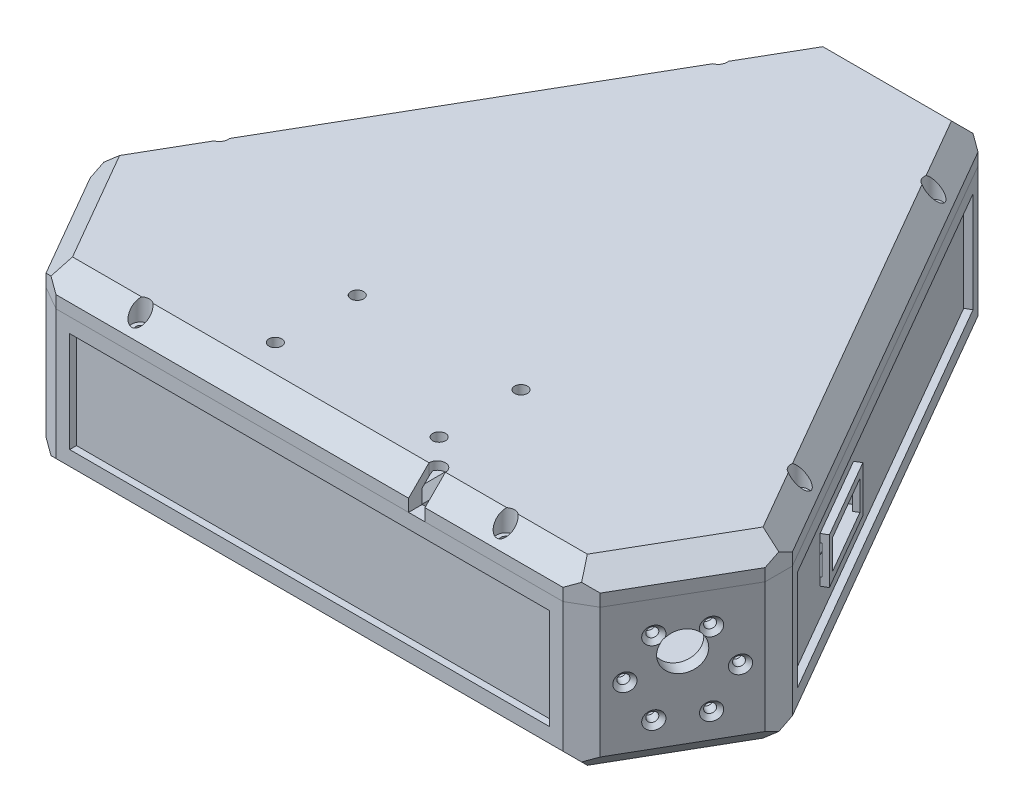
SolidWorks part; units mm, degrees
note: '?' marks a value the reader was unsure of.
ref_plane "Front Plane" through (0, 0, 0) normal (0, 0, 1) x (1, 0, 0)
ref_plane "Top Plane" through (0, 0, 0) normal (0, 1, 0) x (1, 0, 0)
ref_plane "Right Plane" through (0, 0, 0) normal (1, 0, 0) x (0, 0, -1)
ref_axis "Axis1" through (0, 27.75, 0) along (0, -1, 0)?
sketch "Sketch1" plane through (0, 0, 0) normal (0, 1, 0) x (1, 0, 0)
  line L0 (-120.7532, -40.8494) -> (-95.7532, -84.1506)
  line L1 (-95.7532, -84.1506) -> (95.7532, -84.1506)
  line L2 (95.7532, -84.1506) -> (120.7532, -40.8494)
  line L3 (120.7532, -40.8494) -> (25, 125)
  line L4 (25, 125) -> (-25, 125)
  line L5 (-25, 125) -> (-120.7532, -40.8494)
  line L6 (-117.2532, -46.9115) -> (-99.2532, -78.0885) construction
  line L7 (0, 125) -> (0, 0) construction
  line L8 (0, 0) -> (-108.2532, -62.5) construction
  line L9 (0, 0) -> (108.2532, -62.5) construction
  arc A0 (-12.9904, -7.5) -> (12.9904, -7.5) centre (0, 0) ccw construction
  arc A1 (12.9904, -7.5) -> (0, 15) centre (0, 0) ccw construction
  arc A2 (0, 15) -> (-12.9904, -7.5) centre (0, 0) ccw construction
  dimension "D1" = 50
  dimension "D2" = 15
extrude "Outer Ring" add sketch "Sketch1" along normal mid plane 50 thin
sketch "Sketch2" plane through (0, -25, 0) normal (0, -1, 0) x (1, 0, 0)
  line L6 (-126.5267, 40.8494) -> (-27.8868, -130)
  line L7 (-27.8868, -130) -> (27.8868, -130)
  line L8 (27.8868, -130) -> (126.5267, 40.8494)
  line L9 (126.5267, 40.8494) -> (98.6399, 89.1506)
  line L10 (98.6399, 89.1506) -> (-98.6399, 89.1506)
  line L11 (-98.6399, 89.1506) -> (-126.5267, 40.8494)
  line L12 (-126.5267, 40.8494) -> (-27.8868, -130)
  line L13 (-27.8868, -130) -> (27.8868, -130)
  line L14 (27.8868, -130) -> (126.5267, 40.8494)
  line L15 (126.5267, 40.8494) -> (98.6399, 89.1506)
  line L16 (98.6399, 89.1506) -> (-98.6399, 89.1506)
  line L17 (-98.6399, 89.1506) -> (-126.5267, 40.8494)
  dimension "D1" = 0
extrude "Bottom Plate" add sketch "Sketch2" along normal blind 5
fillet "Corner Reinforcement" radius 15 6 edges at (-25, 0, -125) (25, 0, -125) (120.7532, 0, 40.8494) (95.7532, 0, 84.1506) (-95.7532, 0, 84.1506) (-120.7532, 0, 40.8494)
sketch "Sketch3" plane through (0, 25, 0) normal (0, 1, 0) x (1, 0, 0)
  line L0 (-22.1132, 130) -> (-30.7735, 125)
  line L1 (27.8868, 130) -> (-27.8868, 130) construction
  line L2 (-27.8868, 130) -> (-126.5267, -40.8494) construction
  line L3 (22.1132, 130) -> (30.7735, 125)
  line L4 (126.5267, -40.8494) -> (27.8868, 130) construction
  line L5 (-30.7735, 125) -> (-27.8868, 130)
  line L6 (-27.8868, 130) -> (-22.1132, 130)
  line L7 (22.1132, 130) -> (27.8868, 130)
  line L8 (27.8868, 130) -> (30.7735, 125)
  dimension "D1" = 10
extrude "Corner Chamfers" cut sketch "Sketch3" against normal through all both and the other way through all
sketch "Sketch4" plane through (0, 0, -130) normal (0, 0, -1) x (-1, 0, 0)
  circle A0 centre (0, 7) radius 7
  circle A1 centre (0, 7) radius 6 construction
  circle A2 centre (-7.75, 13.4234) radius 1.75
  circle A3 centre (7.75, 13.4234) radius 1.75
  circle A4 centre (-15.5, 0) radius 1.75
  circle A5 centre (15.5, 0) radius 1.75
  circle A6 centre (-7.75, -13.4234) radius 1.75
  circle A7 centre (7.75, -13.4234) radius 1.75
  dimension "D1" = 1
  dimension "D2" = 3.5
extrude "Motor Holes" cut sketch "Sketch4" against normal blind 15
chamfer "Motor Countersinks" distance 1.5 angle 45 6 edges at (-17.25, 0, -130) (-9.5, -13.4234, -130) (6, -13.4234, -130) (13.75, 0, -130) (-9.5, 13.4234, -130) (6, 13.4234, -130)
pattern_circular "CirPattern1" count 3 over 360 about axis through (0, 0, 0) along (0, 1, 0) of "Motor Holes", "Motor Countersinks", "Corner Chamfers"
chamfer "Base Chamfers" distance 7.5 angle 45 18 edges at (0, -30, -130) (-77.2067, -30, -44.5753) (-112.5833, -30, 65) (0, -30, 89.1506) (112.5833, -30, 65) (77.2067, -30, -44.5753) (108.2532, -25, 62.5) (118.4327, -25, 40.8494) (94.5929, -25, 82.141) (72.8766, -25, -42.0753) (0, -25, 84.1506) (23.8397, -25, -122.9904) (-94.5929, -25, 82.141) (0, -25, -125) (-108.2532, -25, 62.5) (-23.8397, -25, -122.9904) (-118.4327, -25, 40.8494) (-72.8766, -25, -42.0753)
sketch "Sketch5" plane through (0, 0, -125) normal (0, 0, 1) x (1, 0, 0)
  circle A0 centre (0, 0) radius 21.25
  circle A1 centre (0, 0) radius 17.25 construction
  circle A2 centre (7.75, 13.4234) radius 1.75 construction
  circle A3 centre (-15.5, 0) radius 1.75 construction
  circle A4 centre (7.75, -13.4234) radius 1.75 construction
  dimension "D1" = 42.5
extrude "Motor Front Clearance" cut sketch "Sketch5" along normal blind 10
sketch "Sketch12" plane through (0, 25, 0) normal (0, 1, 0) x (1, 0, 0)
  line L1 (-29.3301, 117.5) -> (-116.423, -33.3494) construction
  line L5 (29.3301, 117.5) -> (116.423, -33.3494) construction
  line L8 (-36.9338, 104.3301) -> (-41.9338, 95.6699)
  line L9 (36.9338, 104.3301) -> (41.9338, 95.6699)
  line L11 (116.423, -33.3494) -> (29.3301, 117.5) construction
  line L12 (-116.423, -33.3494) -> (-29.3301, 117.5) construction
  line L13 (-39.4338, 100) -> (39.4338, 100) construction
  line L14 (-12.0546, 125) -> (12.0546, 125) construction
  arc A3 (-41.9338, 95.6699) -> (-36.9338, 104.3301) centre (-39.4338, 100) ccw
  arc A5 (36.9338, 104.3301) -> (41.9338, 95.6699) centre (39.4338, 100) ccw
  dimension "D1" = 5
  dimension "D3" = 25
extrude "Lid Lug Bosses" add sketch "Sketch12" against normal blind 7.5
sketch "Sketch13" plane through (0, 25, 0) normal (0, 1, 0) x (1, 0, 0)
  circle A0 centre (-39.4338, 100) radius 2.35
  circle A1 centre (39.4338, 100) radius 2.35
  arc A2 (36.9338, 104.3301) -> (41.9338, 95.6699) centre (39.4338, 100) ccw construction
  arc A3 (-41.9338, 95.6699) -> (-36.9338, 104.3301) centre (-39.4338, 100) ccw construction
  dimension "D1" = 4.7
extrude "Lid Lug Heatset Insert Holes" cut sketch "Sketch13" against normal blind 4
pattern_circular "Lid Lug Pattern" count 3 over 360 about axis through (0, 0, 0) along (0, 1, 0) of "Motor Front Clearance", "Lid Lug Bosses", "Lid Lug Heatset Insert Holes"
chamfer "Lid Lug Chamfer" distance 7.5 angle 30 6 edges at (39.4338, 17.5, -100) (-39.4338, 17.5, -100) (106.3194, 17.5, 15.8494) (66.8857, 17.5, 84.1506) (-66.8857, 17.5, 84.1506) (-106.3194, 17.5, 15.8494)
sketch "Sketch14" plane through (0, 25, 0) normal (0, 1, 0) x (1, 0, 0)
  circle A0 centre (-39.4338, 100) radius 1.75
  circle A1 centre (39.4338, 100) radius 1.75
  circle A2 centre (-106.3194, -15.8494) radius 1.75
  circle A3 centre (-66.8857, -84.1506) radius 1.75
  circle A4 centre (66.8857, -84.1506) radius 1.75
  circle A5 centre (106.3194, -15.8494) radius 1.75
  dimension "D1" = 3.5
extrude "Lid Lug Bolt Clearance" cut sketch "Sketch14" against normal blind 8
fillet "Lid Lug Fillet" radius 3 12 edges at (41.9338, 19.0849, -95.6699) (36.9338, 19.0849, -104.3301) (-36.9338, 19.0849, -104.3301) (-41.9338, 19.0849, -95.6699) (103.8194, 19.0849, 11.5192) (108.8194, 19.0849, 20.1795) (71.8857, 19.0849, 84.1506) (61.8857, 19.0849, 84.1506) (-71.8857, 19.0849, 84.1506) (-61.8857, 19.0849, 84.1506) (-108.8194, 19.0849, 20.1795) (-103.8194, 19.0849, 11.5192)
sketch "Sketch6" plane through (0, -25, 0) normal (0, 1, 0) x (1, 0, 0)
  line L0 (-55.5, 38.5) -> (-55.5, 16.5) construction
  line L1 (-44, 50) -> (44, 50) construction
  line L2 (55.5, 38.5) -> (55.5, 16.5) construction
  line L4 (44, 5) -> (-44, 5) construction
  line L9 (-56.5, 16.5) -> (-56.5, 38.5)
  line L10 (-55.5, 27.5) -> (55.5, 27.5) construction
  line L11 (56.5, 16.5) -> (56.5, 38.5)
  line L23 (-44, 51) -> (44, 51)
  line L24 (-44, 54) -> (44, 54)
  line L25 (-44, 4) -> (44, 4)
  line L26 (-44, 1) -> (44, 1)
  line L27 (-59.5, 38.5) -> (-59.5, 16.5)
  line L28 (59.5, 38.5) -> (59.5, 16.5)
  arc A0 (-44, 51) -> (-56.5, 38.5) centre (-44, 38.5) ccw
  arc A1 (44, 4) -> (56.5, 16.5) centre (44, 16.5) ccw
  arc A2 (-54.776, 20.5159) -> (-39.9841, 5.724) centre (-44, 16.5) ccw construction
  arc A3 (-39.9841, 49.276) -> (-54.776, 34.4841) centre (-44, 38.5) ccw construction
  arc A4 (54.776, 34.4841) -> (39.9841, 49.276) centre (44, 38.5) ccw construction
  arc A5 (39.9841, 5.724) -> (54.776, 20.5159) centre (44, 16.5) ccw construction
  arc A6 (-44, 54) -> (-59.5, 38.5) centre (-44, 38.5) ccw
  arc A7 (44, 1) -> (59.5, 16.5) centre (44, 16.5) ccw
  arc A8 (44, 54) -> (59.5, 38.5) centre (44, 38.5) cw
  arc A9 (44, 51) -> (56.5, 38.5) centre (44, 38.5) cw
  arc A10 (-44, 1) -> (-59.5, 16.5) centre (-44, 16.5) cw
  arc A11 (-44, 4) -> (-56.5, 16.5) centre (-44, 16.5) cw
  dimension "D1" = 1
  dimension "D2" = 3
extrude "Battery Holder" add sketch "Sketch6" along normal blind 20
sketch "Sketch7" plane through (0, 0, -1) normal (0, 0, 1) x (1, 0, 0)
  line L0 (-34, -5) -> (-14, -25)
  line L1 (-44, -5) -> (44, -5) construction
  line L2 (-44, -25) -> (44, -25) construction
  line L3 (-14, -25) -> (14, -25)
  line L4 (14, -25) -> (34, -5)
  line L5 (34, -5) -> (-34, -5)
  line L6 (-44, -5) -> (-44, -25) construction
  point P7 (0, -25)
  point P9 (0, -5)
  dimension "D1" = 45
  dimension "D2" = 10
extrude "Battery Holder Chamfer" cut sketch "Sketch7" against normal up to surface (53 mm away) up to face at (0, -15, -54)
sketch "Sketch8" plane through (0, -25, 0) normal (0, 1, 0) x (1, 0, 0)
  line L0 (0, 0) -> (17, -24.24) construction
  line L1 (-2.05, -9) -> (36.05, -9) construction
  line L2 (-2.05, -9) -> (-2.05, -39.48) construction
  line L3 (-2.05, -39.48) -> (36.05, -39.48) construction
  line L4 (36.05, -9) -> (36.05, -39.48) construction
  line L9 (-2.05, -9) -> (36.05, -39.48) construction
  line L11 (-44, 1) -> (-14, 1) construction
  circle A0 centre (-2.05, -9) radius 2.35
  circle A1 centre (36.05, -9) radius 2.35
  circle A2 centre (-2.05, -39.48) radius 2.35
  circle A3 centre (36.05, -39.48) radius 2.35
  circle A8 centre (36.05, -9) radius 5
  circle A9 centre (-2.05, -9) radius 5
  circle A10 centre (-2.05, -39.48) radius 5
  circle A11 centre (36.05, -39.48) radius 5
  point P7 (17, -24.24)
  dimension "D1" = 38.1
  dimension "D3" = 4.7
  dimension "D4" = 10
  dimension "D2" = 30.48
  dimension "D5" = 10
  dimension "D6" = 17
extrude "Motor Controller Mount" add sketch "Sketch8" along normal blind 15
sketch "Sketch9" plane through (0, -25, 0) normal (0, 1, 0) x (1, 0, 0)
  line L0 (-34, 1) -> (-14, 1) construction
  line L1 (-35.5, -4) -> (-12.45, -4) construction
  line L2 (-35.5, -4) -> (-35.5, -62.05) construction
  line L3 (-35.5, -62.05) -> (-12.45, -62.05) construction
  line L4 (-12.45, -4) -> (-12.45, -62.05) construction
  circle A0 centre (-35.5, -4) radius 0.85
  circle A1 centre (-12.45, -4) radius 0.85
  circle A2 centre (-35.5, -62.05) radius 0.85
  circle A3 centre (-12.45, -62.05) radius 0.85
  circle A4 centre (-35.5, -4) radius 3
  circle A5 centre (-12.45, -4) radius 3
  circle A6 centre (-12.45, -62.05) radius 3
  circle A7 centre (-35.5, -62.05) radius 3
  dimension "D1" = 58.05
  dimension "D3" = 1.7
  dimension "D4" = 6
  dimension "D5" = 5
  dimension "D2" = 23.05
  dimension "D6" = 35.5
extrude "Pi Zero Mount" add sketch "Sketch9" along normal blind 5
chamfer "Chamfer2" distance 3 angle 30 4 edges at (-35.5, -25, 59.05) (-12.45, -25, 59.05) (-35.5, -25, 1) (-12.45, -25, 1)
chamfer "Chamfer3" distance 7.5 angle 30 4 edges at (-2.05, -25, 4) (36.05, -25, 4) (36.05, -25, 34.48) (-2.05, -25, 34.48)
sketch "Sketch10" plane through (0, 0, 84.1506) normal (0, 0, -1) x (-1, 0, 0)
  line L0 (51.975, 19.85) -> (51.975, 16.85)
  line L1 (51.975, 16.85) -> (61.975, 16.85)
  line L2 (61.975, 16.85) -> (61.975, -0.5)
  line L3 (61.975, -0.5) -> (51.975, -0.5)
  line L4 (51.975, -0.5) -> (51.975, -3.5)
  line L5 (51.975, -3.5) -> (61.975, -3.5)
  line L6 (61.975, -3.5) -> (64.975, -0.5)
  line L7 (64.975, -0.5) -> (64.975, 16.85)
  line L8 (64.975, 16.85) -> (61.975, 19.85)
  line L9 (61.975, 19.85) -> (51.975, 19.85)
  line L10 (-24.525, 0) -> (61.475, 0) construction
  line L11 (-24.525, 16.35) -> (61.475, 16.35) construction
  line L12 (61.475, 13.85) -> (61.475, 2.5) construction
  line L13 (61.975, 19.85) -> (61.975, 16.85) construction
  line L14 (64.975, 16.85) -> (61.975, 16.85) construction
  line L15 (18.475, 16.35) -> (18.475, 0) construction
  line L16 (-28.025, 16.85) -> (-25.025, 19.85)
  line L17 (-28.025, -0.5) -> (-28.025, 16.85)
  line L18 (-25.025, -3.5) -> (-28.025, -0.5)
  line L19 (-15.025, -3.5) -> (-25.025, -3.5)
  line L20 (-15.025, -0.5) -> (-15.025, -3.5)
  line L21 (-25.025, -0.5) -> (-15.025, -0.5)
  line L22 (-25.025, 16.85) -> (-25.025, -0.5)
  line L23 (-15.025, 16.85) -> (-25.025, 16.85)
  line L24 (-15.025, 19.85) -> (-15.025, 16.85)
  line L25 (-25.025, 19.85) -> (-15.025, 19.85)
  dimension "D1" = 0.5
  dimension "D2" = 0.5
  dimension "D3" = 0.5
  dimension "D4" = 3
  dimension "D5" = 10
extrude "USB Hub Mount" add sketch "Sketch10" along normal blind 22.5
sketch "Sketch11" plane through (28.025, 0, 0) normal (1, 0, 0) x (0, 0, -1)
  line L0 (-72.6506, 8.175) -> (-61.6506, 8.175) construction
  line L1 (-72.6506, 14.675) -> (-61.6506, 14.675)
  line L2 (-72.6506, 1.675) -> (-61.6506, 1.675)
  line L3 (-61.6506, 16.85) -> (-61.6506, -0.5) construction
  arc A0 (-72.6506, 14.675) -> (-72.6506, 1.675) centre (-72.6506, 8.175) ccw
  arc A1 (-61.6506, 1.675) -> (-61.6506, 14.675) centre (-61.6506, 8.175) ccw
  point P2 (-67.1506, 8.175)
  point P9 (-61.6506, 8.175)
  dimension "D1" = 6.5
  dimension "D2" = 11
extrude "USB Hub Cable Clearance" cut sketch "Sketch11" against normal up to next
chamfer "Chamfer4" distance 15 angle 45 4 edges at (-51.975, -2, 84.1506) (-51.975, 18.35, 84.1506) (15.025, -2, 84.1506) (15.025, 18.35, 84.1506)
chamfer "Chamfer5" distance 0.6 angle 30 24 edges at (-63.475, 18.35, 61.6506) (-64.975, 8.175, 61.6506) (-63.475, -2, 61.6506) (-56.975, -3.5, 61.6506) (-51.975, -2, 61.6506) (-56.975, -0.5, 61.6506) (-61.975, 8.175, 61.6506) (-56.975, 16.85, 61.6506) (-51.975, 18.35, 61.6506) (-56.975, 19.85, 61.6506) (20.025, -0.5, 61.6506) (15.025, -2, 61.6506) (20.025, -3.5, 61.6506) (26.525, -2, 61.6506) (28.025, 0.5875, 61.6506) (26.525, 1.675, 61.6506) (25.025, 0.5875, 61.6506) (26.525, 18.35, 61.6506) (20.025, 19.85, 61.6506) (15.025, 18.35, 61.6506) (20.025, 16.85, 61.6506) (25.025, 15.7625, 61.6506) (26.525, 14.675, 61.6506) (28.025, 15.7625, 61.6506)
sketch "Sketch15" plane through (0, 0, 84.1506) normal (0, 0, -1) x (-1, 0, 0)
  line L1 (61.975, 16.85) -> (59.4695, 16.85)
  line L2 (61.975, 16.85) -> (61.975, 13.1699)
  line L3 (61.975, 13.1699) -> (59.4695, 13.1699)
  line L4 (59.4695, 16.85) -> (59.4695, 13.1699)
extrude "USB Hub Area Lid Lug Removal" cut sketch "Sketch15" along normal up to surface (22.5 mm away) up to face at (-58.6849, 8.175, 61.6506)
sketch "Sketch20" plane through (0, -25, 0) normal (0, 1, 0) x (1, 0, 0)
  line L0 (-98.4384, -17.199) -> (-80.2518, -27.699) construction
  line L1 (-98.4384, -17.199) -> (-76.4384, 20.9061) construction
  line L2 (-80.2518, -27.699) -> (-58.2518, 10.4061) construction
  line L3 (-76.4384, 20.9061) -> (-58.2518, 10.4061) construction
  line L4 (-22.8349, 113.75) -> (-109.9279, -37.0994) construction
  line L5 (-94.6884, -10.7038) -> (-92.7041, -11.8494) construction
  line L6 (-92.7041, -11.8494) -> (-96.4541, -18.3446) construction
  line L7 (-60.2361, 11.5518) -> (-63.9861, 5.0566) construction
  line L8 (-63.9861, 5.0566) -> (-62.0018, 3.9109) construction
  arc A0 (-59.5, 16.5) -> (-44, 1) centre (-44, 16.5) ccw construction
  circle A1 centre (-63.9861, 5.0566) radius 0.85
  circle A2 centre (-92.7041, -11.8494) radius 0.85
  circle A3 centre (-92.7041, -11.8494) radius 3.375
  circle A4 centre (-63.9861, 5.0566) radius 3.375
  dimension "D3" = 7.5
  dimension "D5" = 1.7
  dimension "D6" = 6.75
  dimension "D1" = 44
  dimension "D2" = 21
  dimension "D4" = 2.2913
extrude "Buck Converter Mount" add sketch "Sketch20" along normal blind 5
sketch "Sketch21" plane through (77.2067, 0, -44.5753) normal (0.866, 0, -0.5) x (-0.5, 0, -0.866)
  line L1 (-52.8664, 6.625) -> (-25.3664, 6.625)
  line L2 (-52.8664, 6.625) -> (-52.8664, -4.125)
  line L3 (-52.8664, -4.125) -> (-25.3664, -4.125)
  line L4 (-25.3664, 6.625) -> (-25.3664, -4.125)
  line L5 (-92.8664, -22.5) -> (-92.8664, 25) construction
  line L6 (-52.8664, 25) -> (-52.8664, 6.625) construction
  line L7 (-92.8664, 25) -> (92.8664, 25) construction
  line L8 (-52.8664, -4.125) -> (-52.8664, -22.5) construction
  line L9 (-92.8664, -22.5) -> (92.8664, -22.5) construction
  dimension "D1" = 27.5
  dimension "D2" = 10.75
  dimension "D4" = 40
extrude "Power Switch Hole" cut sketch "Sketch21" against normal up to next
sketch "Sketch22" plane through (72.8766, 0, -42.0753) normal (-0.866, 0, 0.5) x (0.5, 0, 0.866)
  line L0 (25.3664, 6.625) -> (52.8664, 6.625) construction
  line L1 (55.8664, 6.625) -> (22.3664, 6.625)
  line L2 (55.8664, 6.625) -> (55.8664, -4.125)
  line L3 (55.8664, -4.125) -> (22.3664, -4.125)
  line L4 (22.3664, 6.625) -> (22.3664, -4.125)
  line L6 (52.8664, -4.125) -> (25.3664, -4.125) construction
  line L7 (25.3664, -4.125) -> (25.3664, 6.625) construction
  line L8 (25.3664, 6.625) -> (52.8664, 6.625) construction
  point P10 (39.1164, 6.625)
  dimension "D1" = 3
extrude "Power Switch Countersink" cut sketch "Sketch22" against normal offset from surface 2 and the other way blind 5 up to face at (96.7649, 1.25, -10.6995)
sketch "Sketch16" plane through (0, 25, 0) normal (0, 1, 0) x (1, 0, 0)
  line L12 (92.8664, -89.1506) -> (101.5267, -84.1506)
  line L13 (101.5267, -84.1506) -> (123.6399, -45.8494)
  line L14 (123.6399, -45.8494) -> (123.6399, -35.8494)
  line L15 (123.6399, -35.8494) -> (30.7735, 125)
  line L16 (30.7735, 125) -> (22.1132, 130)
  line L17 (22.1132, 130) -> (-22.1132, 130)
  line L18 (-22.1132, 130) -> (-30.7735, 125)
  line L19 (-30.7735, 125) -> (-123.6399, -35.8494)
  line L20 (-123.6399, -35.8494) -> (-123.6399, -45.8494)
  line L21 (-123.6399, -45.8494) -> (-101.5267, -84.1506)
  line L22 (-101.5267, -84.1506) -> (-92.8664, -89.1506)
  line L23 (-92.8664, -89.1506) -> (92.8664, -89.1506)
  line L24 (92.8664, -89.1506) -> (101.5267, -84.1506)
  line L25 (101.5267, -84.1506) -> (123.6399, -45.8494)
  line L26 (123.6399, -45.8494) -> (123.6399, -35.8494)
  line L27 (123.6399, -35.8494) -> (30.7735, 125)
  line L28 (30.7735, 125) -> (22.1132, 130)
  line L29 (22.1132, 130) -> (-22.1132, 130)
  line L30 (-22.1132, 130) -> (-30.7735, 125)
  line L31 (-30.7735, 125) -> (-123.6399, -35.8494)
  line L32 (-123.6399, -35.8494) -> (-123.6399, -45.8494)
  line L33 (-123.6399, -45.8494) -> (-101.5267, -84.1506)
  line L34 (-101.5267, -84.1506) -> (-92.8664, -89.1506)
  line L35 (-92.8664, -89.1506) -> (92.8664, -89.1506)
  dimension "D1" = 0
extrude "Lid Boss" add sketch "Sketch16" along normal blind 12 separate body
chamfer "Lid Chamfer" distance 7.5 angle 45 6 edges at (0, 37, -130) (112.5833, 37, 65) (77.2067, 37, -44.5753) (-77.2067, 37, -44.5753) (-112.5833, 37, 65) (0, 37, 89.1506)
shell "Lid Shell" thickness 3
sketch "Sketch17" plane through (0, 25, 0) normal (0, -1, 0) x (1, 0, 0)
  line L12 (101.5267, 84.1506) -> (92.8664, 89.1506)
  line L13 (123.6399, 45.8494) -> (101.5267, 84.1506)
  line L14 (123.6399, 35.8494) -> (123.6399, 45.8494)
  line L15 (30.7735, -125) -> (123.6399, 35.8494)
  line L16 (22.1132, -130) -> (30.7735, -125)
  line L17 (-22.1132, -130) -> (22.1132, -130)
  line L18 (-30.7735, -125) -> (-22.1132, -130)
  line L19 (-123.6399, 35.8494) -> (-30.7735, -125)
  line L20 (-123.6399, 45.8494) -> (-123.6399, 35.8494)
  line L21 (-101.5267, 84.1506) -> (-123.6399, 45.8494)
  line L22 (-92.8664, 89.1506) -> (-101.5267, 84.1506)
  line L23 (92.8664, 89.1506) -> (-92.8664, 89.1506)
  line L24 (101.5267, 84.1506) -> (92.8664, 89.1506)
  line L25 (123.6399, 45.8494) -> (101.5267, 84.1506)
  line L26 (123.6399, 35.8494) -> (123.6399, 45.8494)
  line L27 (30.7735, -125) -> (123.6399, 35.8494)
  line L28 (22.1132, -130) -> (30.7735, -125)
  line L29 (-22.1132, -130) -> (22.1132, -130)
  line L30 (-30.7735, -125) -> (-22.1132, -130)
  line L31 (-123.6399, 35.8494) -> (-30.7735, -125)
  line L32 (-123.6399, 45.8494) -> (-123.6399, 35.8494)
  line L33 (-101.5267, 84.1506) -> (-123.6399, 45.8494)
  line L34 (-92.8664, 89.1506) -> (-101.5267, 84.1506)
  line L35 (92.8664, 89.1506) -> (-92.8664, 89.1506)
  line L36 (-100.0833, 76.6506) -> (-116.423, 48.3494)
  line L37 (-116.423, 33.3494) -> (-110.0275, 22.272)
  line L38 (-102.6113, 9.4267) -> (-43.1419, -93.5774)
  line L39 (-35.7257, -106.4226) -> (-29.3301, -117.5)
  line L40 (-16.3397, -125) -> (16.3397, -125)
  line L41 (29.3301, -117.5) -> (35.7257, -106.4226)
  line L42 (43.1419, -93.5774) -> (102.6113, 9.4267)
  line L43 (110.0275, 22.272) -> (116.423, 33.3494)
  line L44 (116.423, 48.3494) -> (100.0833, 76.6506)
  line L45 (87.0929, 84.1506) -> (74.3019, 84.1506)
  line L46 (59.4695, 84.1506) -> (-59.4695, 84.1506)
  line L47 (-74.3019, 84.1506) -> (-87.0929, 84.1506)
  line L48 (-100.0833, 76.6506) -> (-116.423, 48.3494)
  line L49 (-116.423, 33.3494) -> (-110.0275, 22.272)
  line L50 (-102.6113, 9.4267) -> (-43.1419, -93.5774)
  line L51 (-35.7257, -106.4226) -> (-29.3301, -117.5)
  line L52 (-16.3397, -125) -> (16.3397, -125)
  line L53 (29.3301, -117.5) -> (35.7257, -106.4226)
  line L54 (43.1419, -93.5774) -> (102.6113, 9.4267)
  line L55 (110.0275, 22.272) -> (116.423, 33.3494)
  line L56 (116.423, 48.3494) -> (100.0833, 76.6506)
  line L57 (87.0929, 84.1506) -> (74.3019, 84.1506)
  line L58 (59.4695, 84.1506) -> (-59.4695, 84.1506)
  line L59 (-74.3019, 84.1506) -> (-87.0929, 84.1506)
  arc A0 (-43.1419, -93.5774) -> (-40.1275, -95.0484) centre (-40.5438, -92.0774) ccw construction
  arc A1 (-43.1419, -93.5774) -> (-40.1275, -95.0484) centre (-40.5438, -92.0774) ccw
  arc A24 (-116.423, 48.3494) -> (-116.423, 33.3494) centre (-103.4327, 40.8494) ccw
  arc A25 (-110.0275, 22.272) -> (-107.0132, 20.801) centre (-107.4294, 23.772) ccw
  arc A26 (-102.3781, 12.7727) -> (-107.0132, 20.801) centre (-106.3194, 15.8494) ccw
  arc A27 (-102.3781, 12.7727) -> (-102.6113, 9.4267) centre (-100.0132, 10.9267) ccw
  arc A28 (-43.1419, -93.5774) -> (-40.1275, -95.0484) centre (-40.5438, -92.0774) ccw
  arc A29 (-35.4924, -103.0766) -> (-40.1275, -95.0484) centre (-39.4338, -100) ccw
  arc A30 (-35.4924, -103.0766) -> (-35.7257, -106.4226) centre (-33.1276, -104.9226) ccw
  arc A31 (-29.3301, -117.5) -> (-16.3397, -125) centre (-16.3397, -110) ccw
  arc A32 (16.3397, -125) -> (29.3301, -117.5) centre (16.3397, -110) ccw
  arc A33 (35.7257, -106.4226) -> (35.4924, -103.0766) centre (33.1276, -104.9226) ccw
  arc A34 (40.1275, -95.0484) -> (35.4924, -103.0766) centre (39.4338, -100) ccw
  arc A35 (40.1275, -95.0484) -> (43.1419, -93.5774) centre (40.5438, -92.0774) ccw
  arc A36 (102.6113, 9.4267) -> (102.3781, 12.7727) centre (100.0132, 10.9267) ccw
  arc A37 (107.0132, 20.801) -> (102.3781, 12.7727) centre (106.3194, 15.8494) ccw
  arc A38 (107.0132, 20.801) -> (110.0275, 22.272) centre (107.4294, 23.772) ccw
  arc A39 (116.423, 33.3494) -> (116.423, 48.3494) centre (103.4327, 40.8494) ccw
  arc A40 (100.0833, 76.6506) -> (87.0929, 84.1506) centre (87.0929, 69.1506) ccw
  arc A41 (74.3019, 84.1506) -> (71.5208, 82.2756) centre (74.3019, 81.1506) ccw
  arc A42 (62.2505, 82.2756) -> (71.5208, 82.2756) centre (66.8857, 84.1506) ccw
  arc A43 (62.2505, 82.2756) -> (59.4695, 84.1506) centre (59.4695, 81.1506) ccw
  arc A44 (-59.4695, 84.1506) -> (-62.2505, 82.2756) centre (-59.4695, 81.1506) ccw
  arc A45 (-71.5208, 82.2756) -> (-62.2505, 82.2756) centre (-66.8857, 84.1506) ccw
  arc A46 (-71.5208, 82.2756) -> (-74.3019, 84.1506) centre (-74.3019, 81.1506) ccw
  arc A47 (-87.0929, 84.1506) -> (-100.0833, 76.6506) centre (-87.0929, 69.1506) ccw
  arc A48 (-116.423, 48.3494) -> (-116.423, 33.3494) centre (-103.4327, 40.8494) ccw
  arc A49 (-110.0275, 22.272) -> (-107.0132, 20.801) centre (-107.4294, 23.772) ccw
  arc A50 (-102.3781, 12.7727) -> (-107.0132, 20.801) centre (-106.3194, 15.8494) ccw
  arc A51 (-102.3781, 12.7727) -> (-102.6113, 9.4267) centre (-100.0132, 10.9267) ccw
  arc A52 (-43.1419, -93.5774) -> (-40.1275, -95.0484) centre (-40.5438, -92.0774) ccw
  arc A53 (-35.4924, -103.0766) -> (-40.1275, -95.0484) centre (-39.4338, -100) ccw
  arc A54 (-35.4924, -103.0766) -> (-35.7257, -106.4226) centre (-33.1276, -104.9226) ccw
  arc A55 (-29.3301, -117.5) -> (-16.3397, -125) centre (-16.3397, -110) ccw
  arc A56 (16.3397, -125) -> (29.3301, -117.5) centre (16.3397, -110) ccw
  arc A57 (35.7257, -106.4226) -> (35.4924, -103.0766) centre (33.1276, -104.9226) ccw
  arc A58 (40.1275, -95.0484) -> (35.4924, -103.0766) centre (39.4338, -100) ccw
  arc A59 (40.1275, -95.0484) -> (43.1419, -93.5774) centre (40.5438, -92.0774) ccw
  arc A60 (102.6113, 9.4267) -> (102.3781, 12.7727) centre (100.0132, 10.9267) ccw
  arc A61 (107.0132, 20.801) -> (102.3781, 12.7727) centre (106.3194, 15.8494) ccw
  arc A62 (107.0132, 20.801) -> (110.0275, 22.272) centre (107.4294, 23.772) ccw
  arc A63 (116.423, 33.3494) -> (116.423, 48.3494) centre (103.4327, 40.8494) ccw
  arc A64 (100.0833, 76.6506) -> (87.0929, 84.1506) centre (87.0929, 69.1506) ccw
  arc A65 (74.3019, 84.1506) -> (71.5208, 82.2756) centre (74.3019, 81.1506) ccw
  arc A66 (62.2505, 82.2756) -> (71.5208, 82.2756) centre (66.8857, 84.1506) ccw
  arc A67 (62.2505, 82.2756) -> (59.4695, 84.1506) centre (59.4695, 81.1506) ccw
  arc A68 (-59.4695, 84.1506) -> (-62.2505, 82.2756) centre (-59.4695, 81.1506) ccw
  arc A69 (-71.5208, 82.2756) -> (-62.2505, 82.2756) centre (-66.8857, 84.1506) ccw
  arc A70 (-71.5208, 82.2756) -> (-74.3019, 84.1506) centre (-74.3019, 81.1506) ccw
  arc A71 (-87.0929, 84.1506) -> (-100.0833, 76.6506) centre (-87.0929, 69.1506) ccw
  line M49 (-99.3305, 81.9545) -> (-92.0626, 86.1506)
  line M50 (-92.0626, 86.1506) -> (92.0626, 86.1506)
  line M51 (92.0626, 86.1506) -> (99.3305, 81.9545)
  line M52 (99.3305, 81.9545) -> (120.6399, 45.0455)
  line M53 (120.6399, 45.0455) -> (120.6399, 36.6532)
  line M54 (120.6399, 36.6532) -> (28.5774, -122.8038)
  line M55 (28.5774, -122.8038) -> (21.3094, -127)
  line M56 (21.3094, -127) -> (-21.3094, -127)
  line M57 (-21.3094, -127) -> (-28.5774, -122.8038)
  line M58 (-28.5774, -122.8038) -> (-120.6399, 36.6532)
  line M59 (-120.6399, 36.6532) -> (-120.6399, 45.0455)
  line M60 (-120.6399, 45.0455) -> (-99.3305, 81.9545)
  line M61 (92.8664, 89.1506) -> (-92.8664, 89.1506)
  line M62 (-92.8664, 89.1506) -> (-101.5267, 84.1506)
  line M63 (-101.5267, 84.1506) -> (-123.6399, 45.8494)
  line M64 (-123.6399, 45.8494) -> (-123.6399, 35.8494)
  line M65 (-123.6399, 35.8494) -> (-30.7735, -125)
  line M66 (-30.7735, -125) -> (-22.1132, -130)
  line M67 (-22.1132, -130) -> (22.1132, -130)
  line M68 (22.1132, -130) -> (30.7735, -125)
  line M69 (30.7735, -125) -> (123.6399, 35.8494)
  line M70 (123.6399, 35.8494) -> (123.6399, 45.8494)
  line M71 (123.6399, 45.8494) -> (101.5267, 84.1506)
  line M72 (101.5267, 84.1506) -> (92.8664, 89.1506)
  dimension "D1" = 0
  dimension "D2" = 0
extrude "Lid Rim" add sketch "Sketch17" against normal up to next contours M72 M61 M62 M63 M64 M65 M66 M67 M68 M69 M70 M71 M60 M49 M50 M51 M52 M53 M54 M55 M56 M57 M58 M59 | A71 L59 A70 A69 A68 L58 A67 A66 A65 L57 A64 L56 A63 L55 A62 A61 A60 L54 A59 A58 A57 L53 A56 L52 A55 L51 A54 A53 A1 L50 A51 A50 A49 L49 A48 L48 M49 M60 M59 M58 M57 M56 M55 M54 M53 M52 M51 M50
sketch "Sketch18" plane through (0, 25, 0) normal (0, -1, 0) x (1, 0, 0)
  circle A0 centre (-106.3194, 15.8494) radius 1.75
  arc A1 (-102.3781, 12.7727) -> (-107.0132, 20.801) centre (-106.3194, 15.8494) ccw construction
  circle A2 centre (-66.8857, 84.1506) radius 1.75
  circle A3 centre (66.8857, 84.1506) radius 1.75
  circle A4 centre (-39.4338, -100) radius 1.75
  circle A5 centre (39.4338, -100) radius 1.75
  circle A6 centre (106.3194, 15.8494) radius 1.75
  arc A7 (-35.4924, -103.0766) -> (-40.1275, -95.0484) centre (-39.4338, -100) ccw construction
  dimension "D1" = 3.5
extrude "Lid Holes" cut sketch "Sketch18" against normal through all
sketch "Sketch19" plane through (0, 25, 0) normal (0, -1, 0) x (1, 0, 0)
  circle A0 centre (-66.8857, 84.1506) radius 3.25
  circle A1 centre (66.8857, 84.1506) radius 3.25
  circle A2 centre (106.3194, 15.8494) radius 3.25
  circle A3 centre (39.4338, -100) radius 3.25
  circle A4 centre (-39.4338, -100) radius 3.25
  circle A5 centre (-106.3194, 15.8494) radius 3.25
  dimension "D1" = 6.5
extrude "Lid Counterbores" cut sketch "Sketch19" against normal through all from offset 4 offset against normal yes
sketch "Sketch23" plane through (0, 37, 0) normal (0, 1, 0) x (1, 0, 0)
  line L0 (0, 0) -> (0, -71.6506) construction
  line L1 (-30, -41.6506) -> (30, -41.6506) construction
  line L2 (-30, -41.6506) -> (-30, -71.6506) construction
  line L3 (-30, -71.6506) -> (30, -71.6506) construction
  line L4 (30, -41.6506) -> (30, -71.6506) construction
  line L5 (-64.809, -81.6506) -> (64.809, -81.6506) construction
  circle A0 centre (30, -71.6506) radius 2.35
  circle A1 centre (30, -41.6506) radius 2.35
  circle A2 centre (-30, -41.6506) radius 2.35
  circle A3 centre (-30, -71.6506) radius 2.35
  dimension "D1" = 4.7
  dimension "D2" = 60
  dimension "D3" = 30
  dimension "D4" = 10
extrude "Camera Mount Holes" cut sketch "Sketch23" against normal up to next (3 mm away)
sketch "Sketch24" plane through (0, 34, 0) normal (0, -1, 0) x (1, 0, 0)
  circle A0 centre (30, 41.6506) radius 5
  circle A1 centre (-30, 41.6506) radius 5
  circle A2 centre (-30, 71.6506) radius 5
  circle A3 centre (30, 71.6506) radius 5
  circle A4 centre (30, 71.6506) radius 2.35 construction
  circle A5 centre (30, 41.6506) radius 2.35 construction
  circle A6 centre (-30, 41.6506) radius 2.35 construction
  circle A7 centre (-30, 71.6506) radius 2.35 construction
  circle A8 centre (30, 71.6506) radius 2.35
  circle A9 centre (30, 41.6506) radius 2.35
  circle A10 centre (-30, 41.6506) radius 2.35
  circle A11 centre (-30, 71.6506) radius 2.35
  dimension "D1" = 10
extrude "Boss-Extrude9" add sketch "Sketch24" along normal blind 2.5
chamfer "Chamfer8" distance 3 angle 45 4 edges at (30, 34, 76.6506) (30, 34, 46.6506) (-30, 34, 46.6506) (-30, 34, 76.6506)
sketch "Sketch25" plane through (0, 31.5, 0) normal (0, -1, 0) x (1, 0, 0)
  circle A0 centre (-30, 41.6506) radius 5.5 construction
  circle A1 centre (30, 41.6506) radius 5.5 construction
  circle A2 centre (30, 71.6506) radius 5.5 construction
  circle A3 centre (-30, 71.6506) radius 5.5 construction
  circle A4 centre (-30, 41.6506) radius 5.5
  circle A5 centre (30, 41.6506) radius 5.5
  circle A6 centre (30, 71.6506) radius 5.5
  circle A7 centre (-30, 71.6506) radius 5.5
  circle A8 centre (-30, 41.6506) radius 1.75
  circle A9 centre (30, 41.6506) radius 1.75
  circle A10 centre (30, 71.6506) radius 1.75
  circle A11 centre (-30, 71.6506) radius 1.75
  dimension "D1" = 3.5
extrude "Boss-Extrude10" add sketch "Sketch25" against normal offset from surface (1.5 mm away) 4 up to face at (-30, 37, 74.0006)
sketch "Sketch26" plane through (0, 37, 0) normal (0, 1, 0) x (1, 0, 0)
  line L0 (39.3098, -89.1506) -> (39.3098, -81.6506) construction
  line L1 (92.8664, -89.1506) -> (-92.8664, -89.1506) construction
  line L2 (-64.809, -81.6506) -> (64.809, -81.6506) construction
  line L3 (36.3098, -89.1506) -> (36.3098, -81.6506)
  line L4 (42.3098, -89.1506) -> (42.3098, -81.6506)
  arc A0 (36.3098, -89.1506) -> (42.3098, -89.1506) centre (39.3098, -89.1506) ccw
  arc A1 (42.3098, -81.6506) -> (36.3098, -81.6506) centre (39.3098, -81.6506) ccw
  point P6 (39.3098, -85.4006)
  dimension "D1" = 3
  dimension "D2" = 55
extrude "Cut-Extrude14" cut sketch "Sketch26" against normal through all
sketch "Sketch27" plane through (0, 0, 89.1506) normal (0, 0, 1) x (1, 0, 0)
  line L0 (87.8664, 19.65) -> (-87.8664, 19.65)
  line L2 (-87.8664, 19.65) -> (-87.8664, -17.1543)
  line L4 (87.8664, 1.25) -> (87.8664, 19.65)
  line L5 (87.8664, 1.25) -> (87.8664, -17.1543)
  line L7 (-87.8664, -17.1543) -> (87.8664, -17.1543)
  dimension "D1" = 18.4043
  dimension "D2" = 18.4
extrude "Cut-Extrude17" cut sketch "Sketch27" against normal blind 2.5
sketch "Sketch28" plane through (77.2067, 0, -44.5753) normal (0.866, 0, -0.5) x (-0.5, 0, -0.866)
  line L0 (-25.3664, 6.625) -> (-52.8664, 6.625) construction
  line L1 (-55.8664, 9.625) -> (-22.3664, 9.625)
  line L2 (-55.8664, 9.625) -> (-55.8664, -7.125)
  line L3 (-55.8664, -7.125) -> (-22.3664, -7.125)
  line L4 (-22.3664, 9.625) -> (-22.3664, -7.125)
  line L5 (-52.8664, -4.125) -> (-25.3664, -4.125) construction
  line L6 (-25.3664, -4.125) -> (-25.3664, 6.625) construction
  line L7 (-52.8664, 6.625) -> (-52.8664, -4.125) construction
  line L8 (-92.8664, -22.5) -> (-92.8664, 25) construction
  line L10 (-87.8664, 19.65) -> (87.8664, 19.65)
  line L11 (-87.8664, 19.65) -> (-87.8664, -17.15)
  line L12 (-87.8664, -17.15) -> (87.8664, -17.15)
  line L13 (87.8664, 19.65) -> (87.8664, -17.15)
  line L14 (92.8664, -22.5) -> (92.8664, 25) construction
  line L15 (-92.8664, -22.5) -> (92.8664, -22.5) construction
  line L17 (-92.8664, 25) -> (92.8664, 25) construction
  dimension "D1" = 3
  dimension "D2" = 3
  dimension "D3" = 3
  dimension "D4" = 3
  dimension "D5" = 5
  dimension "D6" = 5
  dimension "D7" = 5.35
  dimension "D8" = 5.35
extrude "Cut-Extrude18" cut sketch "Sketch28" against normal blind 2.5
sketch "Sketch29" plane through (-77.2067, 0, -44.5753) normal (-0.866, 0, -0.5) x (-0.5, 0, 0.866)
  line L0 (-92.8664, -22.5) -> (-92.8664, 25) construction
  line L1 (-87.8664, 19.65) -> (87.8664, 19.65)
  line L2 (-87.8664, 19.65) -> (-87.8664, -17.15)
  line L3 (-87.8664, -17.15) -> (87.8664, -17.15)
  line L4 (87.8664, 19.65) -> (87.8664, -17.15)
  line L5 (92.8664, -22.5) -> (92.8664, 25) construction
  line L6 (-92.8664, 25) -> (92.8664, 25) construction
  line L7 (-92.8664, -22.5) -> (92.8664, -22.5) construction
  dimension "D1" = 5
  dimension "D2" = 5
  dimension "D3" = 5.35
  dimension "D4" = 5.35
extrude "Cut-Extrude19" cut sketch "Sketch29" against normal blind 2.5
